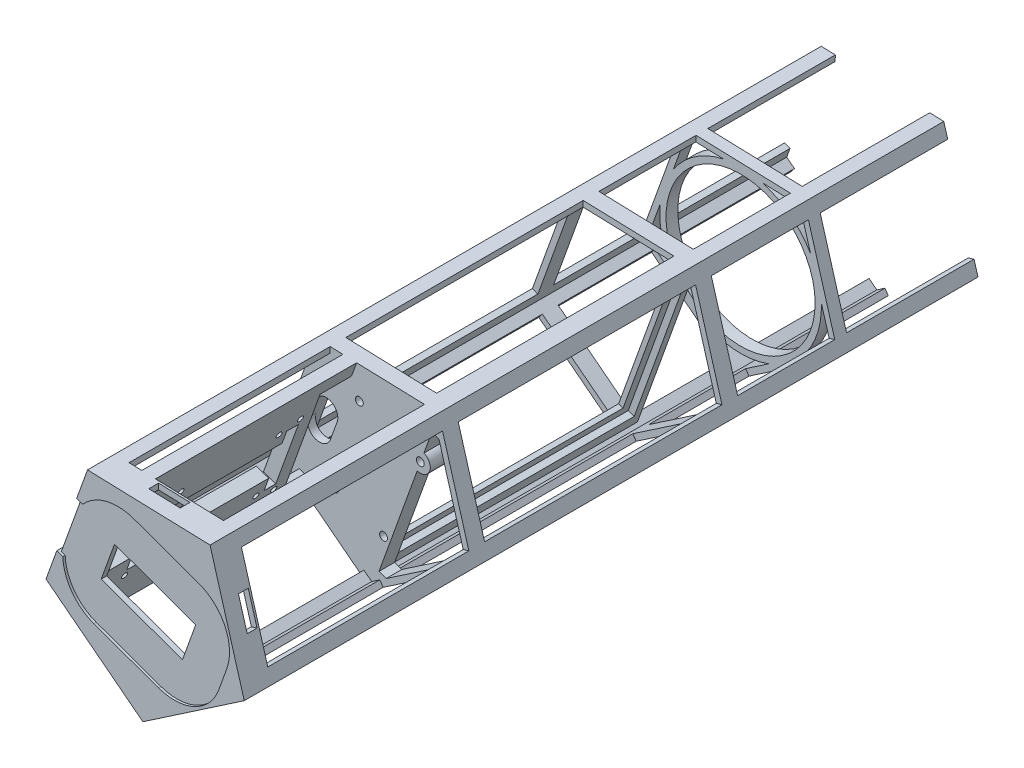
SolidWorks part; units mm, degrees
ref_plane "Front Plane" through (0, 0, 0) normal (0, 0, 1) x (1, 0, 0)
ref_plane "Top Plane" through (0, 0, 0) normal (0, 1, 0) x (1, 0, 0)
ref_plane "Right Plane" through (0, 0, 0) normal (1, 0, 0) x (0, 0, -1)
sketch "Sketch3" plane through (0, 0, 0) normal (0, 0, 1) x (1, 0, 0)
  line L0 (0, 0) -> (16.2851, 21.0012) construction
  line L1 (15.1489, 19.536) -> (-13.8986, 20.4445)
  line L2 (-13.8986, 20.4445) -> (-23.7387, -6.9006)
  line L3 (-23.7387, -6.9006) -> (-0.7728, -24.7093)
  line L4 (-0.7728, -24.7093) -> (23.2611, -8.3705)
  line L5 (0, 0) -> (29.9163, 0) construction
  line L6 (0, 0) -> (25.0057, -8.9983) construction
  line L10 (-0.8307, -26.5625) -> (25.0057, -8.9983)
  line L11 (25.0057, -8.9983) -> (16.2851, 21.0012)
  line L12 (16.2851, 21.0012) -> (-14.941, 21.9778)
  line L13 (-14.941, 21.9778) -> (-25.5191, -7.4182)
  line L14 (-25.5191, -7.4182) -> (-0.8307, -26.5625)
  line L15 (23.2611, -8.3705) -> (15.1489, 19.536)
  circle A0 centre (0, 0) radius 20 construction
  dimension "D2" = 40
extrude "Boss-Extrude2" add sketch "Sketch3" along normal blind 185
ref_plane "Plane1" through (0, 0, 92.5) normal (0, 0, 1) x (1, 0, 0)
sketch "Sketch4" plane through (0, 0, 0) normal (0, 0, -1) x (-1, 0, 0)
  line L0 (14.745, 18.0921) -> (16.1564, 18.6)
  line L1 (13.8986, 20.4445) -> (23.7387, -6.9006) construction
  line L2 (14.941, 21.9778) -> (25.5191, -7.4182) construction
  line L3 (24.3036, -4.0404) -> (22.8922, -4.5483)
  line L4 (22.8922, -4.5483) -> (14.745, 18.0921)
  line L5 (24.3036, -4.0404) -> (16.1564, 18.6)
  dimension "D1" = 2.5
  dimension "D2" = 2.5
extrude "Cut-Extrude1" cut sketch "Sketch4" against normal offset from surface (180 mm away) 5 up to face at (0, 0, 185)
ref_point "Point1"
ref_axis "Axis1" through (0, 0, 185) along (0, 0, 1)
pattern_circular "CirPattern1" count 5 over 360 about axis through (0, 0, 185) along (0, 0, 1) of "Cut-Extrude1"
ref_plane "Plane2" through (0, 0, 92.5) normal (0, 0, 1) x (1, 0, 0)
sketch "Sketch5" plane through (0, 0, 92.5) normal (0, 0, 1) x (1, 0, 0)
  line L0 (-2.0696, -25.6018) -> (14.7182, 21.0502) construction
  line L2 (-24.1133, -8.5083) -> (-1.8275, -25.7895) construction
  line L3 (23.2611, -8.3705) -> (0, 0) construction
  line L4 (-4.3961, -23.7977) -> (11.7756, 21.1422)
  line L8 (-2.0696, -25.6018) -> (-4.3961, -23.7977)
  line L10 (14.7182, 21.0502) -> (11.7756, 21.1422)
  line L11 (-2.0696, -25.6018) -> (14.7182, 21.0502)
  line L12 (-22.8004, 22.2236) -> (6.2471, 21.3151) construction
  dimension "D1" = 18
  dimension "D2" = 2.8
extrude "Boss-Extrude3" add sketch "Sketch5" along normal mid plane 64.5
sketch "Sketch6" plane through (0, 0, 124.75) normal (0, 0, 1) x (1, 0, 0)
  line L5 (-25.5191, -7.4182) -> (-0.8307, -26.5625)
  line L6 (-0.8307, -26.5625) -> (25.0057, -8.9983)
  line L7 (25.0057, -8.9983) -> (16.2851, 21.0012)
  line L8 (16.2851, 21.0012) -> (-14.941, 21.9778)
  line L9 (-14.941, 21.9778) -> (-25.5191, -7.4182)
  line L10 (-25.5191, -7.4182) -> (-0.8307, -26.5625)
  line L11 (-0.8307, -26.5625) -> (25.0057, -8.9983)
  line L12 (25.0057, -8.9983) -> (16.2851, 21.0012)
  line L13 (16.2851, 21.0012) -> (-14.941, 21.9778)
  line L14 (-14.941, 21.9778) -> (-25.5191, -7.4182)
  dimension "D1" = 0
extrude "Boss-Extrude4" add sketch "Sketch6" along normal blind 4
sketch "Sketch7" plane through (0, 0, 124.75) normal (0, 0, -1) x (-1, 0, 0)
  line L0 (-3.6897, -1.3278) -> (20.23, 7.2798) construction
  line L1 (-11.7756, 21.1422) -> (4.3961, -23.7977) construction
  line L2 (16.1564, 18.6) -> (24.3036, -4.0404) construction
  line L4 (19.0326, -2.4504) -> (13.1071, 14.0159)
  line L5 (0.2139, -9.2223) -> (-5.7115, 7.244)
  line L7 (19.0326, -2.4504) -> (-5.7115, 7.244) construction
  line L8 (0.2139, -9.2223) -> (13.1071, 14.0159) construction
  line L9 (9.6232, -5.8364) -> (3.6978, 10.63) construction
  line L11 (-11.7756, 21.1422) -> (4.3961, -23.7977) construction
  arc A0 (-5.7115, 7.244) -> (13.1071, 14.0159) centre (3.6978, 10.63) cw
  arc A1 (0.2139, -9.2223) -> (19.0326, -2.4504) centre (9.6232, -5.8364) ccw
  point P7 (6.6605, 2.3968)
  point P9 (13.0092, -15.2457)
  point P14 (0.3119, 20.0393)
  dimension "D1" = 37.5
  dimension "D2" = 20
  dimension "D3" = 1
extrude "Cut-Extrude2" cut sketch "Sketch7" against normal blind 2
sketch "Sketch8" plane through (6.3243, -2.2758, 0) normal (0.9409, -0.3386, 0) x (0, 0, -1)
  line L0 (-60.25, 0) -> (-124.75, 0) construction
  line L1 (-124.75, -23.2131) -> (-124.75, 23.2131) construction
  line L3 (-60.25, -23.2131) -> (-60.25, 23.2131) construction
  line L5 (-123, -20.5) -> (-123, 20.5)
  line L6 (-123, -20.5) -> (-62, -20.5)
  line L7 (-123, 20.5) -> (-62, 20.5)
  line L8 (-62, -20.5) -> (-62, 20.5)
  line L14 (-62, 20.5) -> (-123, -20.5) construction
  line L15 (-62, -20.5) -> (-123, 20.5) construction
  point P11 (-92.5, 0)
  point P14 (-92.5, 0)
  dimension "D1" = 61
  dimension "D2" = 41
extrude "Cut-Extrude3" cut sketch "Sketch8" against normal blind 1.6
sketch "Sketch9" plane through (4.8189, -1.7341, 0) normal (0.9409, -0.3386, 0) x (0, 0, -1)
  line L8 (-121, -18.5) -> (-64, -18.5)
  line L9 (-64, -18.5) -> (-64, 18.5)
  line L10 (-64, 18.5) -> (-121, 18.5)
  line L11 (-121, 18.5) -> (-121, -18.5)
  line L12 (-121, -18.5) -> (-64, -18.5)
  line L13 (-64, -18.5) -> (-64, 18.5)
  line L14 (-64, 18.5) -> (-121, 18.5)
  line L15 (-121, 18.5) -> (-121, -18.5)
  dimension "D1" = 2
extrude "Cut-Extrude4" cut sketch "Sketch9" against normal up to surface (1.2 mm away) up to face at (3.6897, -1.3278, 92.5)
sketch "Sketch10" plane through (0, 0, 60.25) normal (0, 0, -1) x (-1, 0, 0)
  line L25 (-23.2611, -8.3705) -> (0.7728, -24.7093)
  line L26 (0.7728, -24.7093) -> (23.7387, -6.9006)
  line L27 (23.7387, -6.9006) -> (13.8986, 20.4445)
  line L28 (13.8986, 20.4445) -> (-15.1489, 19.536)
  line L29 (-15.1489, 19.536) -> (-23.2611, -8.3705)
  line L30 (0.8307, -26.5625) -> (25.5191, -7.4182)
  line L31 (-25.0057, -8.9983) -> (0.8307, -26.5625)
  line L32 (-16.2851, 21.0012) -> (-25.0057, -8.9983)
  line L33 (14.941, 21.9778) -> (-16.2851, 21.0012)
  line L34 (25.5191, -7.4182) -> (14.941, 21.9778)
  line L40 (0.8307, -26.5625) -> (25.5191, -7.4182)
  line L41 (-25.0057, -8.9983) -> (0.8307, -26.5625)
  line L42 (-16.2851, 21.0012) -> (-25.0057, -8.9983)
  line L43 (14.941, 21.9778) -> (-16.2851, 21.0012)
  line L44 (25.5191, -7.4182) -> (14.941, 21.9778)
  dimension "D1" = 0
extrude "Boss-Extrude5" add sketch "Sketch10" against normal blind 4
sketch "Sketch11" plane through (0, 0, 60.25) normal (0, 0, -1) x (-1, 0, 0)
  line L0 (3.8621, -22.3137) -> (4.3961, -23.7977)
  line L1 (4.3961, -23.7977) -> (3.6676, -24.3627)
  line L2 (-11.2416, 19.6582) -> (-11.7756, 21.1422)
  line L3 (-11.7756, 21.1422) -> (-12.697, 21.1134)
  line L4 (21.7631, -8.4326) -> (3.8621, -22.3137)
  line L7 (3.8621, -22.3137) -> (-11.2416, 19.6582)
  line L9 (-14.1842, 19.5662) -> (1.5355, -24.1178)
  line L10 (-14.1842, 19.5662) -> (1.5355, -24.1178)
  line L11 (-12.697, 21.1134) -> (11.3529, 21.8656) construction
  line L13 (3.8621, -22.3137) -> (-11.2416, 19.6582) construction
  line L18 (22.6823, -9.618) -> (3.6676, -24.3627) construction
  line L19 (3.8621, -22.3137) -> (-11.2416, 19.6582)
  line L27 (-11.2416, 19.6582) -> (11.3998, 20.3663)
  line L31 (1.5355, -24.1178) -> (2.7484, -23.1773)
  line L33 (1.5355, -24.1178) -> (2.7484, -23.1773)
  line L35 (2.7484, -23.1773) -> (3.6676, -24.3627)
  line L37 (2.7484, -23.1773) -> (3.6676, -24.3627)
  line L39 (3.6676, -24.3627) -> (22.6823, -9.618)
  line L41 (22.6823, -9.618) -> (21.7631, -8.4326)
  line L43 (11.3998, 20.3663) -> (11.3529, 21.8656)
  line L45 (11.3529, 21.8656) -> (-12.697, 21.1134)
  line L47 (-12.697, 21.1134) -> (-12.6502, 19.6141)
  line L48 (-12.697, 21.1134) -> (-12.6502, 19.6141)
  line L49 (-12.6502, 19.6141) -> (-14.1842, 19.5662)
  line L50 (-12.6502, 19.6141) -> (-14.1842, 19.5662)
  dimension "D1" = 0
ref_plane "Plane3" through (0, 0, 32.5) normal (0, 0, 1) x (1, 0, 0)
sketch "Sketch14" plane through (0, 0, 32.5) normal (0, 0, 1) x (1, 0, 0)
  line L5 (-25.5191, -7.4182) -> (-0.8307, -26.5625)
  line L6 (-0.8307, -26.5625) -> (25.0057, -8.9983)
  line L7 (25.0057, -8.9983) -> (16.2851, 21.0012)
  line L8 (16.2851, 21.0012) -> (-14.941, 21.9778)
  line L9 (-14.941, 21.9778) -> (-25.5191, -7.4182)
  line L11 (-0.8307, -26.5625) -> (25.0057, -8.9983)
  line L12 (25.0057, -8.9983) -> (16.2851, 21.0012)
  line L16 (23.2611, -8.3705) -> (15.3259, -13.7651)
  line L18 (-0.7728, -24.7093) -> (-8.3554, -18.8294)
  line L20 (-23.7387, -6.9006) -> (-20.4898, 2.1279)
  line L22 (-13.8986, 20.4445) -> (-4.308, 20.1445)
  line L24 (15.1489, 19.536) -> (17.8273, 10.3221)
  line L25 (7.1625, -19.3147) -> (-0.7728, -24.7093)
  line L26 (20.5827, 0.8433) -> (23.2611, -8.3705)
  line L27 (5.5584, 19.8359) -> (15.1489, 19.536)
  line L28 (-17.1475, 11.416) -> (-13.8986, 20.4445)
  line L29 (-16.1561, -12.7805) -> (-23.7387, -6.9006)
  line L30 (16.2851, 21.0012) -> (-14.941, 21.9778)
  line L31 (-14.941, 21.9778) -> (-25.5191, -7.4182)
  line L32 (-25.5191, -7.4182) -> (-0.8307, -26.5625)
  circle A3 centre (0, 0) radius 19
  arc A8 (15.3259, -13.7651) -> (20.5827, 0.8433) centre (0, 0) ccw
  circle A9 centre (0, 0) radius 20.6 construction
  arc A10 (17.8273, 10.3221) -> (5.5584, 19.8359) centre (0, 0) ccw
  arc A11 (-4.308, 20.1445) -> (-17.1475, 11.416) centre (0, 0) ccw
  arc A12 (-20.4898, 2.1279) -> (-16.1561, -12.7805) centre (0, 0) ccw
  arc A13 (-8.3554, -18.8294) -> (7.1625, -19.3147) centre (0, 0) ccw
  dimension "D2" = 38
  dimension "D1" = 0
  dimension "D3" = 1.6
extrude "Boss-Extrude8" add sketch "Sketch14" along normal blind 3
ref_plane "Plane4" through (0, 0, 29.5) normal (0, 0, -1) x (-1, 0, 0)
sketch "Sketch15" plane through (0, 0, 29.5) normal (0, 0, -1) x (-1, 0, 0)
  line L0 (-23.2611, -8.3705) -> (0.7728, -24.7093)
  line L1 (0.7728, -24.7093) -> (23.7387, -6.9006)
  line L2 (23.7387, -6.9006) -> (13.8986, 20.4445)
  line L3 (13.8986, 20.4445) -> (-15.1489, 19.536)
  line L4 (-15.1489, 19.536) -> (-23.2611, -8.3705)
  line L5 (0.8307, -26.5625) -> (25.5191, -7.4182)
  line L6 (-25.0057, -8.9983) -> (0.8307, -26.5625)
  line L7 (-16.2851, 21.0012) -> (-25.0057, -8.9983)
  line L8 (14.941, 21.9778) -> (-16.2851, 21.0012)
  line L9 (25.5191, -7.4182) -> (14.941, 21.9778)
  line L10 (0.8307, -26.5625) -> (25.5191, -7.4182)
  line L11 (-25.0057, -8.9983) -> (0.8307, -26.5625)
  line L12 (-16.2851, 21.0012) -> (-25.0057, -8.9983)
  line L13 (14.941, 21.9778) -> (-16.2851, 21.0012)
  line L14 (25.5191, -7.4182) -> (14.941, 21.9778)
  dimension "D1" = 0
sketch "Sketch29" plane through (0, 0, 185) normal (0, 0, 1) x (1, 0, 0)
  line L5 (-25.5191, -7.4182) -> (-0.8307, -26.5625)
  line L6 (-0.8307, -26.5625) -> (25.0057, -8.9983)
  line L7 (25.0057, -8.9983) -> (16.2851, 21.0012)
  line L8 (16.2851, 21.0012) -> (-14.941, 21.9778)
  line L9 (-14.941, 21.9778) -> (-25.5191, -7.4182)
  line L10 (-25.5191, -7.4182) -> (-0.8307, -26.5625)
  line L11 (-0.8307, -26.5625) -> (25.0057, -8.9983)
  line L12 (25.0057, -8.9983) -> (16.2851, 21.0012)
  line L13 (16.2851, 21.0012) -> (-14.941, 21.9778)
  line L14 (-14.941, 21.9778) -> (-25.5191, -7.4182)
  dimension "D1" = 0
extrude "Boss-Extrude13" add sketch "Sketch29" along normal blind 2
sketch "Sketch30" plane through (0, 0, 187) normal (0, 0, 1) x (1, 0, 0)
  line L0 (25.0057, -8.9983) -> (-20.23, 7.2798) construction
  line L1 (-14.941, 21.9778) -> (-25.5191, -7.4182) construction
  line L2 (3.1542, -17.0767) -> (-13.3121, -11.1513)
  line L3 (18.5086, -9.8487) -> (20.5401, -4.2031)
  line L4 (-20.5401, 4.2031) -> (-18.5086, 9.8487)
  line L5 (13.3121, 11.1513) -> (-3.1542, 17.0767)
  line L6 (14.4454, -21.1398) -> (-14.4454, 21.1398) construction
  line L7 (-24.6033, -7.0881) -> (24.6033, 7.0881) construction
  line L8 (19.5243, -7.0259) -> (-19.5243, 7.0259) construction
  arc A0 (18.5086, -9.8487) -> (3.1542, -17.0767) centre (7.2174, -5.7855) cw
  arc A1 (-18.5086, 9.8487) -> (-3.1542, 17.0767) centre (-7.2174, 5.7855) cw
  arc A2 (-13.3121, -11.1513) -> (-20.5401, 4.2031) centre (-9.2489, 0.1399) cw
  arc A3 (20.5401, -4.2031) -> (13.3121, 11.1513) centre (9.2489, -0.1399) ccw
  point P5 (0, 0)
  dimension "D3" = 12
  dimension "D1" = 30
  dimension "D2" = 41.5
extrude "Cut-Extrude8" cut sketch "Sketch30" against normal blind 0.6
sketch "Sketch31" plane through (0, 0, 186.4) normal (0, 0, 1) x (1, 0, 0)
  line L0 (25.0057, -8.9983) -> (0, 0) construction
  line L1 (12.0432, 0.9801) -> (8.6573, -8.4292)
  line L2 (12.0432, 0.9801) -> (-8.6573, 8.4292)
  line L3 (8.6573, -8.4292) -> (-12.0432, -0.9801)
  line L4 (-8.6573, 8.4292) -> (-12.0432, -0.9801)
  line L5 (12.0432, 0.9801) -> (-12.0432, -0.9801) construction
  line L6 (8.6573, -8.4292) -> (-8.6573, 8.4292) construction
  line L7 (-10.3503, 3.7246) -> (10.3503, -3.7246) construction
  dimension "D1" = 22
  dimension "D2" = 10
extrude "Cut-Extrude9" cut sketch "Sketch31" against normal up to surface (1.4 mm away) up to face at (0, 0, 185)
sketch "Sketch32" plane through (0, 0, 187) normal (0, 0, 1) x (1, 0, 0)
  line L0 (0, 0) -> (-36.3954, 13.0969) construction
  line L1 (-22.7695, 0.2228) -> (-21.2398, -0.3276)
  line L3 (-14.941, 21.9778) -> (-25.5191, -7.4182) construction
  line L4 (-17.6906, 14.3368) -> (-16.1609, 13.7863)
  line L5 (-18.5086, 9.8487) -> (-20.5401, 4.2031) construction
  line L6 (-18.5086, 9.8487) -> (-20.5401, 4.2031)
  line L7 (-17.6906, 14.3368) -> (-22.7695, 0.2228)
  arc A0 (-20.5401, 4.2031) -> (-13.3121, -11.1513) centre (-9.2489, 0.1399) ccw construction
  arc A1 (-20.5401, 4.2031) -> (-13.3121, -11.1513) centre (-9.2489, 0.1399) ccw construction
  arc A3 (-3.1542, 17.0767) -> (-18.5086, 9.8487) centre (-7.2174, 5.7855) ccw construction
  arc A4 (-16.1609, 13.7863) -> (-18.5086, 9.8487) centre (-7.2174, 5.7855) ccw
  arc A5 (-20.5401, 4.2031) -> (-21.2398, -0.3276) centre (-9.2489, 0.1399) ccw
  dimension "D1" = 7.5
extrude "Cut-Extrude11" cut sketch "Sketch32" against normal up to surface (0.6 mm away) up to face at (0, 0, 186.4)
sketch "Sketch34" plane through (0, 0, 186.4) normal (0, 0, 1) x (1, 0, 0)
  line L0 (-22.7695, 0.2228) -> (-17.6906, 14.3368)
  line L1 (-22.7695, 0.2228) -> (-22.0638, -0.0311)
  line L2 (-17.6906, 14.3368) -> (-16.9849, 14.0828)
  line L3 (-22.0638, -0.0311) -> (-16.9849, 14.0828)
  line L4 (-13.3121, -11.1513) -> (3.1542, -17.0767)
  line L5 (18.5086, -9.8487) -> (20.5401, -4.2031)
  line L6 (13.3121, 11.1513) -> (-3.1542, 17.0767)
  line L7 (-18.5086, 9.8487) -> (-20.5401, 4.2031)
  line L8 (-13.3121, -11.1513) -> (3.1542, -17.0767) construction
  line L9 (18.5086, -9.8487) -> (20.5401, -4.2031) construction
  line L10 (13.3121, 11.1513) -> (-3.1542, 17.0767) construction
  line L11 (-18.5086, 9.8487) -> (-20.5401, 4.2031) construction
  arc A4 (3.1542, -17.0767) -> (18.5086, -9.8487) centre (7.2174, -5.7855) ccw
  arc A5 (20.5401, -4.2031) -> (13.3121, 11.1513) centre (9.2489, -0.1399) ccw
  arc A6 (-3.1542, 17.0767) -> (-18.5086, 9.8487) centre (-7.2174, 5.7855) ccw
  arc A7 (-20.5401, 4.2031) -> (-13.3121, -11.1513) centre (-9.2489, 0.1399) ccw
  arc A8 (3.1542, -17.0767) -> (18.5086, -9.8487) centre (7.2174, -5.7855) ccw construction
  arc A9 (20.5401, -4.2031) -> (13.3121, 11.1513) centre (9.2489, -0.1399) ccw construction
  arc A10 (-3.1542, 17.0767) -> (-18.5086, 9.8487) centre (-7.2174, 5.7855) ccw construction
  arc A11 (-20.5401, 4.2031) -> (-13.3121, -11.1513) centre (-9.2489, 0.1399) ccw construction
  dimension "D1" = 0
sketch "Sketch38" plane through (0, 0, 124.75) normal (0, 0, -1) x (-1, 0, 0)
  line L5 (13.8986, 20.4445) -> (-15.1489, 19.536)
  line L6 (-15.1489, 19.536) -> (-23.2611, -8.3705)
  line L7 (-23.2611, -8.3705) -> (0.7728, -24.7093)
  line L8 (0.7728, -24.7093) -> (23.7387, -6.9006)
  line L9 (23.7387, -6.9006) -> (13.8986, 20.4445)
  line L11 (-16.3988, 15.2363) -> (-23.2611, -8.3705)
  line L12 (-23.2611, -8.3705) -> (-2.9303, -22.1919)
  line L16 (-1.0956, -21.5316) -> (-2.9303, -22.1919)
  line L17 (0.03, -24.6596) -> (-15.6897, 19.0244)
  line L18 (-1.0956, -21.5316) -> (-14.5641, 15.8965)
  line L19 (-14.5641, 15.8965) -> (-16.3988, 15.2363)
  dimension "D3" = 1.6
  dimension "D4" = 1.6
  dimension "D1" = 0
  dimension "D2" = 1.6
extrude "Cut-Extrude14" cut sketch "Sketch38" against normal up to surface (4 mm away) up to face at (0, 0, 128.75)
sketch "Sketch40" plane through (-18.8186, 6.7719, 0) normal (0.9409, -0.3386, 0) x (0, 0, -1)
  line L0 (-185, 14.5309) -> (-185, -14.5309) construction
  line L1 (-185, 7.5) -> (-183.5, 7.5)
  line L2 (-185, 7.5) -> (-185, -7.5)
  line L3 (-185, -7.5) -> (-183.5, -7.5)
  line L4 (-183.5, 7.5) -> (-183.5, -7.5)
  line L5 (-183.5, 0) -> (-185, 0) construction
  point P9 (-185, 0)
  dimension "D1" = 15
  dimension "D2" = 1.5
extrude "Cut-Extrude15" cut sketch "Sketch40" against normal up to surface (1.5 mm away) up to face at (-20.23, 7.2798, 98.8167)
sketch "Sketch41" plane through (-20.23, 7.2798, 0) normal (-0.9409, 0.3386, 0) x (0, 0, 1)
  line L0 (185, -7.5) -> (186.4, -7.5)
  line L1 (185, 7.5) -> (186.4, 7.5)
  line L2 (185, -7.5) -> (185, 7.5)
  line L3 (186.4, 7.5) -> (186.4, -7.5)
extrude "Cut-Extrude16" cut sketch "Sketch41" against normal blind 0.6
ref_plane "Plane5" through (14.5641, 15.8965, 124.75) normal (0.3386, 0.9409, 0) x (0.9409, -0.3386, 0)
sketch "Sketch42" plane through (0, 0, 128.75) normal (0, 0, 1) x (1, 0, 0)
  line L0 (-20.23, 7.2798) -> (0, 0) construction
  line L1 (-16.1564, 18.6) -> (-24.3036, -4.0404) construction
  line L2 (5.4365, -16.774) -> (-14.8782, -9.4637) construction
  line L3 (5.4365, -16.774) -> (14.8782, 9.4637) construction
  line L4 (-14.8782, -9.4637) -> (-5.4365, 16.774) construction
  line L5 (14.8782, 9.4637) -> (-5.4365, 16.774) construction
  line L6 (5.4365, -16.774) -> (-5.4365, 16.774) construction
  line L7 (-14.8782, -9.4637) -> (14.8782, 9.4637) construction
  line L8 (-3.9066, 13.524) -> (11.6282, 7.9338) construction
  line L9 (4.7208, 13.1189) -> (-4.7208, -13.1189) construction
  line L10 (2.2472, -13.2032) -> (-10.1449, -8.7439) construction
  line L11 (-1.5355, -24.1178) -> (14.1842, 19.5662) construction
  line L12 (-1.5355, -24.1178) -> (14.1842, 19.5662)
  line L13 (12.891, 3.9416) -> (6.1392, -14.8212) construction
  line L14 (12.891, 3.9416) -> (10.6328, 4.7542) construction
  line L15 (6.1392, -14.8212) -> (3.881, -14.0086) construction
  line L16 (10.6328, 4.7542) -> (3.881, -14.0086) construction
  circle A0 centre (11.6282, 7.9338) radius 1
  circle A1 centre (-3.9066, 13.524) radius 1
  circle A2 centre (2.2472, -13.2032) radius 1
  circle A3 centre (-10.1449, -8.7439) radius 1
  point P1 (3.8608, 10.7289)
  point P2 (0, 0)
  point P19 (-3.9488, -10.9735)
  dimension "D4" = 2
  dimension "D7" = 2
  dimension "D1" = 21.59
  dimension "D2" = 27.8848
  dimension "D3" = 16.51
  dimension "D5" = 2.54
  dimension "D6" = 13.17
  dimension "D8" = 2.28
  dimension "D9" = 2.4
sketch "Sketch43" plane through (0, 0, 128.75) normal (0, 0, 1) x (1, 0, 0)
  line L1 (10.8306, 5.5214) -> (12.5507, 10.3013)
  line L2 (12.891, 3.9416) -> (10.6328, 4.7542) construction
  line L3 (12.891, 3.9416) -> (10.6328, 4.7542)
  line L4 (1.0956, -21.5316) -> (14.5641, 15.8965) construction
  arc A0 (12.5507, 10.3013) -> (10.8306, 5.5214) centre (11.6282, 7.9338) cw
  point P4 (12.5507, 10.3013)
  line M27 (1.0956, -21.5316) -> (14.5641, 15.8965)
  dimension "D1" = 2.5409
extrude "Boss-Extrude15" add sketch "Sketch43" against normal up to surface (4 mm away) contours A0 M27 region at (12.6767, 7.5565, 128.75) up to face at (11.7736, -4.2367, 124.75)
sketch "Sketch44" plane through (0, 0, 128.75) normal (0, 0, 1) x (1, 0, 0)
  circle A0 centre (-10.1449, -8.7439) radius 1 construction
  circle A1 centre (-3.9066, 13.524) radius 1 construction
  circle A2 centre (-10.1449, -8.7439) radius 1
  circle A3 centre (-3.9066, 13.524) radius 1
extrude "Cut-Extrude18" cut sketch "Sketch42" against normal blind 3.5 contours A0 | A2
extrude "Cut-Extrude19" cut sketch "Sketch44" against normal blind 1.5
sketch "Sketch45" plane through (0, 0, 128.75) normal (0, 0, 1) x (1, 0, 0)
  line L0 (-2.5743, -18.735) -> (9.9537, 16.0795) construction
  line L1 (-2.5743, -18.735) -> (9.9537, 16.0795) construction
  line L2 (13.2655, 17.0133) -> (-0.6169, -21.5649) construction
  line L3 (13.2655, 17.0133) -> (-0.6169, -21.5649) construction
  line L4 (-4.3961, -23.7977) -> (11.7756, 21.1422)
  line L5 (11.7756, 21.1422) -> (14.7182, 21.0502)
  line L6 (14.7182, 21.0502) -> (-2.0696, -25.6018)
  line L7 (-2.0696, -25.6018) -> (-4.3961, -23.7977)
  line L8 (-22.6823, -9.618) -> (-3.6676, -24.3627) construction
  line L11 (12.697, 21.1134) -> (-11.3529, 21.8656) construction
sketch "Sketch46" plane through (0, 0, 128.75) normal (0, 0, 1) x (1, 0, 0)
  line L0 (-8.1098, 21.7641) -> (-20.1403, -11.5891)
  line L1 (-8.1098, 21.7641) -> (-4.6098, 21.6547)
  line L2 (-20.1403, -11.5891) -> (-17.3745, -13.7339)
  line L3 (-4.6098, 21.6547) -> (-17.3745, -13.7339)
  line L4 (-16.1564, 18.6) -> (-24.3036, -4.0404) construction
  line L5 (-1.5355, -24.1178) -> (14.1842, 19.5662) construction
  line L6 (-1.5355, -24.1178) -> (14.1842, 19.5662)
  line L8 (12.697, 21.1134) -> (-11.3529, 21.8656) construction
  line L9 (-22.6823, -9.618) -> (-3.6676, -24.3627) construction
  line M13 (12.697, 21.1134) -> (-11.3529, 21.8656)
  line M23 (-22.6823, -9.618) -> (-3.6676, -24.3627)
  dimension "D1" = 3.5
  dimension "D2" = 3.5
  dimension "D3" = 6.5
extrude "Boss-Extrude17" add sketch "Sketch46" along normal up to surface (56.25 mm away) contours L3 L0 M13 M23 region at (-12.5431, 4.5184, 128.75) up to face at (-8.552, 3.0775, 185)
sketch "Sketch48" plane through (-14.1227, 5.0941, 0) normal (-0.9407, 0.3393, 0) x (0, 0, 1)
  line L0 (128.75, 18.8059) -> (128.75, -18.8143) construction
  line L1 (128.75, -15) -> (136.75, -15)
  line L2 (128.75, -15) -> (128.75, 15)
  line L3 (128.75, 15) -> (136.75, 15)
  line L4 (136.75, -15) -> (136.75, 15)
  line L5 (128.75, -15) -> (136.75, 15) construction
  line L6 (128.75, 15) -> (136.75, -15) construction
  line L7 (-3.5596, 0) -> (269.0596, 0) construction
  point P0 (132.75, 0)
  dimension "D1" = 8
  dimension "D2" = 30
extrude "Cut-Extrude20" cut sketch "Sketch48" against normal up to surface (3.3295 mm away) up to face at (-10.9922, 3.9602, 168.4375)
sketch "Sketch49" plane through (0, 0, 126.75) normal (0, 0, -1) x (-1, 0, 0)
  line L0 (-2.7488, -0.9892) -> (16.0698, 5.7828) construction
  line L1 (-5.7115, 7.244) -> (0.2139, -9.2223) construction
  line L2 (19.0326, -2.4504) -> (13.1071, 14.0159) construction
  line L3 (12.4006, 7.1193) -> (14.0935, 2.4146) construction
  line L4 (15.2234, 8.1351) -> (16.9163, 3.4304)
  line L5 (9.5778, 6.1035) -> (11.2707, 1.3988)
  arc A0 (15.2234, 8.1351) -> (9.5778, 6.1035) centre (12.4006, 7.1193) ccw
  arc A1 (11.2707, 1.3988) -> (16.9163, 3.4304) centre (14.0935, 2.4146) ccw
  point P8 (13.247, 4.767)
  dimension "D1" = 6
  dimension "D2" = 5
extrude "Cut-Extrude21" cut sketch "Sketch49" against normal up to surface (10 mm away) up to face at (-12.5567, 4.5292, 136.75)
sketch "Sketch50" plane through (-14.1227, 5.0941, 0) normal (-0.9407, 0.3393, 0) x (0, 0, 1)
  line L0 (136.75, 0) -> (181.403, 0) construction
  line L1 (138.0765, -12.1) -> (180.0765, -12.1) construction
  line L2 (138.0765, -12.1) -> (138.0765, 12.1) construction
  line L3 (138.0765, 12.1) -> (180.0765, 12.1) construction
  line L4 (180.0765, -12.1) -> (180.0765, 12.1) construction
  line L5 (138.0765, -12.1) -> (180.0765, 12.1) construction
  line L6 (138.0765, 12.1) -> (180.0765, -12.1) construction
  line L7 (136.75, -15) -> (136.75, 15) construction
  line L8 (159.0765, 12.1) -> (159.0765, -12.1) construction
  circle A0 centre (178.0765, -10.1) radius 0.75
  circle A1 centre (178.0765, 10.1) radius 0.75
  circle A2 centre (140.0765, -10.1) radius 0.75
  circle A3 centre (140.0765, 10.1) radius 0.75
  point P0 (159.0765, 0)
  point P5 (178.0765, -10.85)
  point P6 (178.8265, -10.1)
  dimension "D3" = 1.5
  dimension "D4" = 1.25
  dimension "D1" = 24.2
  dimension "D2" = 42
  dimension "D5" = 1.25
extrude "Cut-Extrude22" cut sketch "Sketch50" against normal up to surface (3.3295 mm away) up to face at (-10.9917, 3.9616, 156.5417)
sketch "Sketch51" plane through (-14.1227, 5.0941, 0) normal (-0.9407, 0.3393, 0) x (0, 0, 1)
  line L0 (180, 0) -> (103.153, 0) construction
  line L1 (143.0765, -8.5) -> (140.0765, -8.5)
  line L2 (143.0765, -8.5) -> (143.0765, -4.9557)
  line L3 (143.0765, 8.5) -> (140.0765, 8.5)
  line L4 (140.0765, -8.5) -> (140.0765, 8.5)
  line L5 (143.0765, -8.5) -> (140.0765, 8.5) construction
  line L6 (143.0765, 8.5) -> (140.0765, -8.5) construction
  line L7 (180, -12.047) -> (180, 12.0147) construction
  line L8 (140.0765, 10.1) -> (140.0765, -10.1) construction
  line L9 (178.0765, 10.1) -> (178.0765, 5.0443) construction
  line L10 (140.0765, 10.1) -> (178.0765, -10.1) construction
  line L11 (140.0765, -10.1) -> (178.0765, 10.1) construction
  line L12 (159.0765, 10.1) -> (159.0765, -10.1) construction
  line L13 (175.0765, 8.5) -> (178.0765, 8.5)
  line L14 (178.0765, -8.5) -> (178.0765, -4.9557)
  line L15 (175.0765, -8.5) -> (178.0765, -8.5)
  line L16 (175.0765, -8.5) -> (175.0765, -4.9557)
  line L17 (143.0765, 5.0443) -> (175.0765, 5.0443)
  line L20 (143.0765, -4.9557) -> (175.0765, -4.9557)
  line L21 (143.0765, 5.0443) -> (175.0765, -4.9557) construction
  line L22 (175.0765, 5.0443) -> (143.0765, -4.9557) construction
  line L23 (143.0765, 5.0443) -> (143.0765, 8.5)
  line L24 (175.0765, 5.0443) -> (175.0765, 8.5)
  line L25 (178.0765, 5.0443) -> (185, 5.0443)
  line L26 (185, 5.0443) -> (185, -4.9557)
  line L27 (185, -4.9557) -> (178.0765, -4.9557)
  line L28 (178.0765, -4.9557) -> (178.0765, -10.1) construction
  line L29 (178.0765, 5.0443) -> (178.0765, 8.5)
  line L30 (185, 16.1438) -> (185, -16.1585) construction
  point P0 (141.5765, 0)
  point P21 (159.0765, 0)
  point P26 (159.0765, 0.0443)
  dimension "D1" = 17
  dimension "D2" = 10
  dimension "D3" = 3
  dimension "D4" = 3.5443
extrude "Cut-Extrude23" cut sketch "Sketch51" against normal up to surface (3.3295 mm away) up to face at (-7.3093, 14.1707, 178.0765)
sketch "Sketch52" plane through (-10.9907, 3.9644, 0) normal (0.9407, -0.3393, 0) x (0, 0, -1)
  line L0 (-170.0765, 8.75) -> (-170.0765, -8.75) construction
  line L1 (-140.0765, 0) -> (-178.0765, 0) construction
  line L2 (-140.0765, 8.5) -> (-140.0765, -8.5) construction
  line L3 (-178.0765, -8.5) -> (-178.0765, -4.9557) construction
  line L4 (-145.0765, 8.75) -> (-145.0765, -8.75) construction
  circle A0 centre (-170.0765, 8.75) radius 0.75
  circle A1 centre (-170.0765, -8.75) radius 0.75
  circle A2 centre (-145.0765, 8.75) radius 0.75
  circle A3 centre (-145.0765, -8.75) radius 0.75
  point P10 (-170.0765, 0)
  point P16 (-145.0765, 0)
  dimension "D1" = 1.5
  dimension "D2" = 17.5
  dimension "D3" = 8
  dimension "D4" = 25
extrude "Cut-Extrude24" cut sketch "Sketch52" against normal up to surface (3.3295 mm away) up to face at (-14.1191, 5.104, 161.199)
sketch "Sketch53" plane through (-20.23, 7.2798, 0) normal (-0.9409, 0.3386, 0) x (0, 0, 1)
  line L0 (183, -4) -> (180.5, -4)
  line L1 (183, -4) -> (183, 4)
  line L2 (180.5, -4) -> (180.5, 4)
  line L3 (183, 4) -> (180.5, 4)
  line L4 (183, -4) -> (180.5, 4) construction
  line L5 (180.5, -4) -> (183, 4) construction
  line L7 (183.5, 0) -> (180, 0) construction
  line L8 (183.5, 7.5) -> (183.5, -7.5) construction
  line L9 (180, -12.0309) -> (180, 12.0309) construction
  point P1 (181.75, 0)
  dimension "D1" = 2.5
  dimension "D2" = 8
extrude "Cut-Extrude25" cut sketch "Sketch53" against normal up to surface (1.5 mm away) up to face at (-18.8186, 6.7719, 165.1667)
pattern_circular "CirPattern5" count 5 over 360 about axis through (0, 0, 185) along (0, 0, 1) of "Cut-Extrude25"
sketch "Sketch54" plane through (4.8189, -1.7341, 0) normal (0.9409, -0.3386, 0) x (0, 0, -1)
  line L0 (-62, 20.5) -> (-123, 20.5) construction
  line L1 (-123, 20.5) -> (-123, -20.5) construction
  line L2 (-64, 0) -> (-121, 0) construction
  line L3 (-64, -18.5) -> (-64, 18.5) construction
  line L4 (-121, 18.5) -> (-121, -18.5) construction
  line L5 (-92.5, 18.5) -> (-92.5, -18.5) construction
  line L6 (-64, 18.5) -> (-121, 18.5) construction
  line L7 (-121, -18.5) -> (-64, -18.5) construction
  circle A0 centre (-122, 19.5) radius 0.5
  circle A1 centre (-122, -19.5) radius 0.5
  circle A2 centre (-63, -19.5) radius 0.5
  circle A3 centre (-63, 19.5) radius 0.5
  dimension "D1" = 1
  dimension "D2" = 1
  dimension "D3" = 1
ref_plane "Plane8" through (15.2997, 42.5167, 0) normal (-0.3386, -0.9409, 0) x (-0.9409, 0.3386, 0)
